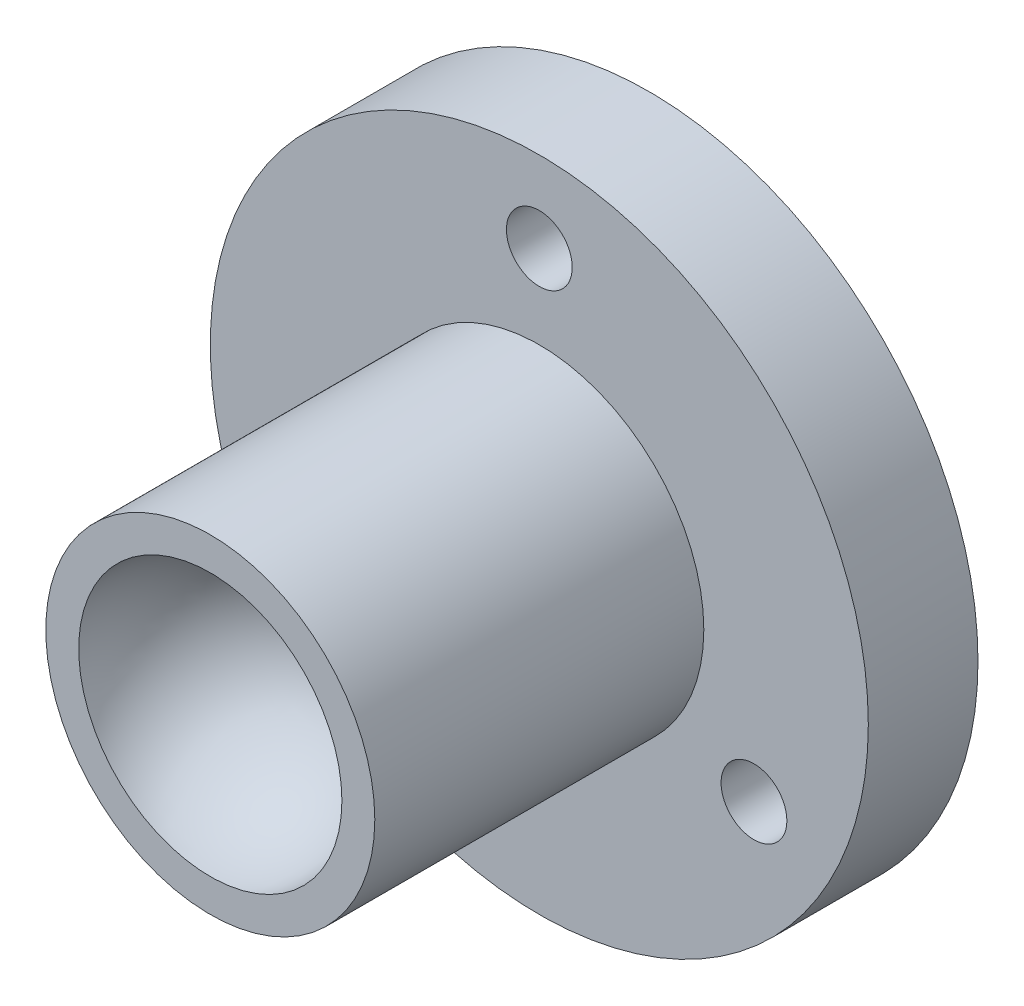
SolidWorks part; units mm, degrees
ref_plane "Front Plane" through (0, 0, 0) normal (0, 0, 1) x (1, 0, 0)
ref_plane "Top Plane" through (0, 0, 0) normal (0, 1, 0) x (1, 0, 0)
ref_plane "Right Plane" through (0, 0, 0) normal (1, 0, 0) x (0, 0, -1)
sketch "Sketch1" plane through (0, 0, 0) normal (0, 0, 1) x (1, 0, 0)
  circle A3 centre (0, 0) radius 15
  circle A4 centre (0, 0) radius 7.5
  circle A5 centre (0, 0) radius 6
  dimension "D1" = 30
  dimension "D2" = 15
  dimension "D3" = 12
extrude "Boss-Extrude1" add sketch "Sketch1" along normal blind 20 contours A4 A5 region at (-7.2879, 0, 0)
extrude "Boss-Extrude2" add sketch "Sketch1<4>" along normal blind 20 contours A5 region at (0, 0, 0)
sketch "Sketch1<4>" plane through (0, 0, 0) normal (0, 0, 1) x (1, 0, 0) same geometry as "Sketch1"
extrude "Boss-Extrude3" add sketch "Sketch1<5>" along normal blind 5 contours A3 A4 region at (-14.5757, 0, 0)
sketch "Sketch1<5>" plane through (0, 0, 0) normal (0, 0, 1) x (1, 0, 0) same geometry as "Sketch1"
sketch "Sketch2" plane through (0, 0, 20) normal (0, 0, 1) x (1, 0, 0)
  line L0 (0, 6) -> (0, -6)
  line L1 (0, 13.7853) -> (0, -13.7853) construction
  arc A0 (0, 6) -> (0, -6) centre (0, 0) cw
  point P5 (0, 0)
  point P10 (0, 0)
  dimension "D2" = 6
  dimension "D1" = 12
revolve "Cut-Revolve1" cut sketch "Sketch2" angle 360 about L1
sketch "Sketch3" plane through (0, 0, 5) normal (0, 0, 1) x (1, 0, 0)
  circle A0 centre (0, 11.3) radius 1.5
  circle A1 centre (9.7861, -5.65) radius 1.5
  circle A2 centre (-9.7861, -5.65) radius 1.5
  point P9 (0, 0)
  dimension "D1" = 11.3
  dimension "D2" = 3
extrude "Cut-Extrude1" cut sketch "Sketch3" against normal blind 11
scale "Scale1" scale about centroid uniform scaling yes scale factor 0.5
scale "Scale2" scale about centroid uniform scaling yes scale factor 1.25
scale "Scale3" scale about centroid uniform scaling yes scale factor 1.1
